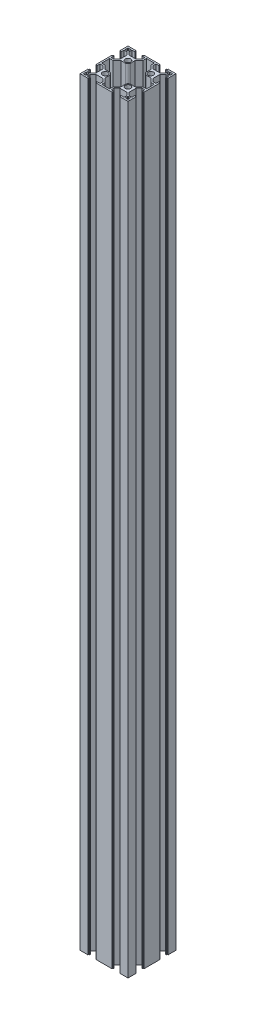
SolidWorks part; units mm, degrees
ref_plane "Front Plane" through (0, 0, 0) normal (0, 0, 1) x (1, 0, 0)
ref_plane "Top Plane" through (0, 0, 0) normal (0, 1, 0) x (1, 0, 0)
ref_plane "Right Plane" through (0, 0, 0) normal (1, 0, 0) x (0, 0, -1)
sketch "Sketch1" plane through (0, 0, 0) normal (0, 1, 0) x (1, 0, 0)
  line L0 (0, 30) -> (0, -30) construction
  line L1 (-30, -30) -> (30, -30)
  line L2 (-30, -30) -> (-30, 30)
  line L3 (-30, 30) -> (30, 30)
  line L4 (30, -30) -> (30, 30)
  line L5 (-30, -30) -> (30, 30) construction
  line L6 (-30, 30) -> (30, -30) construction
  line L7 (-30, 0) -> (30, 0) construction
  line L8 (-23.05, -28) -> (-6.95, -28)
  line L9 (-6.95, -28) -> (-6.95, -24.4)
  line L10 (-6.95, -24.4) -> (-10.615, -20.8)
  line L11 (-10.615, -20.8) -> (-19.385, -20.8)
  line L12 (-19.385, -20.8) -> (-23.05, -24.4)
  line L13 (-23.05, -24.4) -> (-23.05, -28)
  line L14 (10.615, -20.8) -> (19.385, -20.8)
  line L15 (6.95, -24.4) -> (10.615, -20.8)
  line L16 (6.95, -28) -> (6.95, -24.4)
  line L17 (23.05, -28) -> (6.95, -28)
  line L18 (23.05, -24.4) -> (23.05, -28)
  line L19 (19.385, -20.8) -> (23.05, -24.4)
  line L20 (19.385, 20.8) -> (23.05, 24.4)
  line L21 (23.05, 24.4) -> (23.05, 28)
  line L22 (23.05, 28) -> (6.95, 28)
  line L23 (6.95, 28) -> (6.95, 24.4)
  line L24 (6.95, 24.4) -> (10.615, 20.8)
  line L25 (10.615, 20.8) -> (19.385, 20.8)
  line L26 (-23.05, 24.4) -> (-23.05, 28)
  line L27 (-19.385, 20.8) -> (-23.05, 24.4)
  line L28 (-10.615, 20.8) -> (-19.385, 20.8)
  line L29 (-6.95, 24.4) -> (-10.615, 20.8)
  line L30 (-6.95, 28) -> (-6.95, 24.4)
  line L31 (-23.05, 28) -> (-6.95, 28)
  line L32 (-20.8, 19.385) -> (-24.4, 23.05)
  line L33 (-24.4, 23.05) -> (-28, 23.05)
  line L34 (-28, 23.05) -> (-28, 6.95)
  line L35 (-28, 6.95) -> (-24.4, 6.95)
  line L36 (-24.4, 6.95) -> (-20.8, 10.615)
  line L37 (-20.8, 10.615) -> (-20.8, 19.385)
  line L38 (-24.4, -23.05) -> (-28, -23.05)
  line L39 (-20.8, -19.385) -> (-24.4, -23.05)
  line L40 (-20.8, -10.615) -> (-20.8, -19.385)
  line L41 (-24.4, -6.95) -> (-20.8, -10.615)
  line L42 (-28, -6.95) -> (-24.4, -6.95)
  line L43 (-28, -23.05) -> (-28, -6.95)
  line L44 (20.8, -19.385) -> (24.4, -23.05)
  line L45 (24.4, -23.05) -> (28, -23.05)
  line L46 (28, -23.05) -> (28, -6.95)
  line L47 (28, -6.95) -> (24.4, -6.95)
  line L48 (24.4, -6.95) -> (20.8, -10.615)
  line L49 (20.8, -10.615) -> (20.8, -19.385)
  line L50 (24.4, 23.05) -> (28, 23.05)
  line L51 (20.8, 19.385) -> (24.4, 23.05)
  line L52 (20.8, 10.615) -> (20.8, 19.385)
  line L53 (24.4, 6.95) -> (20.8, 10.615)
  line L54 (28, 6.95) -> (24.4, 6.95)
  line L55 (28, 23.05) -> (28, 6.95)
  point P0 (0, 0)
  dimension "D1" = 60
  dimension "D2" = 16.1
  dimension "D3" = 8.77
  dimension "D4" = 3.6
  dimension "D5" = 7.2
  dimension "D6" = 2
  dimension "D7" = 6.95
extrude "Boss-Extrude1" add sketch "Sketch1" along normal blind 950
sketch "Sketch2" plane through (0, 950, 0) normal (0, 1, 0) x (1, 0, 0)
  line L0 (-19.1, -28) -> (-19.1, -29)
  line L1 (-23.05, -28) -> (-6.95, -28) construction
  line L2 (-30, -30) -> (30, -30) construction
  line L3 (-10.9, -28) -> (-10.9, -29)
  line L4 (-10.9, -29) -> (-9.9, -29)
  line L5 (-9.9, -29) -> (-9.9, -30)
  line L6 (-19.1, -29) -> (-20.1, -29)
  line L7 (-20.1, -29) -> (-20.1, -30)
  line L8 (-19.1, -28) -> (-10.9, -28)
  line L9 (-20.1, -30) -> (-9.9, -30)
  dimension "D1" = 8.2
  dimension "D2" = 3.95
  dimension "D3" = 1
  dimension "D4" = 1
extrude "Cut-Extrude1" cut sketch "Sketch2" against normal through all
mirror "Mirror1" about plane through (0, 0, 0) normal (1, 0, 0) of "Cut-Extrude1"
ref_axis "Axis1" through (0, 1050, 0) along (0, -1, 0)
pattern_circular "CirPattern1" count 4 over 360 about axis through (0, 1050, 0) along (0, -1, 0) of "Cut-Extrude1", "Mirror1"
sketch "Sketch4" plane through (0, 950, 0) normal (0, 1, 0) x (1, 0, 0)
  line L0 (19.385, 18.8) -> (9.797, 18.8) construction
  line L1 (-18.8, 18.8) -> (-18.8, 9.797)
  line L2 (18.8, -19.385) -> (18.8, -9.797) construction
  line L3 (28, 4.95) -> (28, -4.95)
  line L4 (-18.8, -9.797) -> (-18.8, -19.385) construction
  line L5 (4.95, -28) -> (-4.95, -28)
  line L6 (-9.797, 18.8) -> (-9.797, 13.197)
  line L7 (-28, -4.95) -> (-28, 4.95)
  line L8 (-18.8, 9.797) -> (-23.5611, 4.95)
  line L9 (-23.5611, 4.95) -> (-28, 4.95)
  line L10 (18.8, 18.8) -> (9.797, 18.8)
  line L11 (9.797, 18.8) -> (4.95, 23.5611)
  line L12 (4.95, 23.5611) -> (4.95, 28)
  line L13 (4.95, 28) -> (4.95, 28)
  line L14 (4.95, 28) -> (4.95, 28)
  line L15 (4.95, 28) -> (4.95, 28)
  line L16 (4.95, 28) -> (4.95, 28)
  line L17 (4.95, 28) -> (-4.95, 28)
  line L18 (-4.95, 28) -> (-4.95, 28)
  line L19 (-4.95, 28) -> (-4.95, 28)
  line L20 (-4.95, 28) -> (-4.95, 28)
  line L21 (-4.95, 28) -> (-4.95, 28)
  line L22 (-4.95, 28) -> (-4.95, 23.5611)
  line L23 (-4.95, 23.5611) -> (-9.797, 18.8)
  line L24 (-9.797, 18.8) -> (-18.8, 18.8)
  line L25 (28, 4.95) -> (23.5611, 4.95)
  line L26 (23.5611, 4.95) -> (18.8, 9.797)
  line L27 (18.8, 9.797) -> (18.8, 18.8)
  line L28 (18.8, -18.8) -> (18.8, -9.797)
  line L29 (18.8, -9.797) -> (23.5611, -4.95)
  line L30 (23.5611, -4.95) -> (28, -4.95)
  line L31 (4.95, -28) -> (4.95, -23.5611)
  line L32 (4.95, -23.5611) -> (9.797, -18.8)
  line L33 (9.797, -18.8) -> (18.8, -18.8)
  line L34 (-18.8, -18.8) -> (-9.797, -18.8)
  line L35 (-9.797, -18.8) -> (-4.95, -23.5611)
  line L36 (-4.95, -23.5611) -> (-4.95, -28)
  line L37 (-28, -4.95) -> (-23.5611, -4.95)
  line L38 (-23.5611, -4.95) -> (-18.8, -9.797)
  line L39 (-18.8, -9.797) -> (-18.8, -18.8)
  line L40 (-9.797, 18.8) -> (-19.385, 18.8) construction
  line L41 (-18.8, 19.385) -> (-18.8, 9.797) construction
  line L42 (18.8, 9.797) -> (18.8, 19.385) construction
  line L43 (9.797, -18.8) -> (19.385, -18.8) construction
  line L44 (-19.385, -18.8) -> (-9.797, -18.8) construction
  line L45 (-13.197, 9.797) -> (-18.8, 9.797)
  line L46 (9.797, 18.8) -> (9.797, 13.197)
  line L47 (13.197, 9.797) -> (18.8, 9.797)
  line L48 (-18.8, -9.797) -> (-13.197, -9.797)
  line L49 (-9.797, -13.197) -> (-9.797, -18.8)
  line L50 (9.797, -18.8) -> (9.797, -13.197)
  line L51 (13.197, -9.797) -> (18.8, -9.797)
  line L52 (-27.5, -28) -> (-24.9, -28)
  line L53 (24.9, -28) -> (27.5, -28)
  line L54 (24.4, -27.5) -> (24.4, -24.9)
  line L55 (24.9, -24.4) -> (27.5, -24.4)
  line L56 (28, -27.5) -> (28, -24.9)
  line L57 (24.4, -28) -> (28, -24.4) construction
  line L58 (24.4, -24.4) -> (28, -28) construction
  line L59 (-28, -24.9) -> (-28, -27.5)
  line L60 (-27.5, -24.4) -> (-24.9, -24.4)
  line L61 (-24.4, -24.9) -> (-24.4, -27.5)
  line L62 (-28, 27.5) -> (-28, 24.9)
  line L63 (-24.9, 28) -> (-27.5, 28)
  line L64 (-24.4, 27.5) -> (-24.4, 24.9)
  line L65 (-24.9, 24.4) -> (-27.5, 24.4)
  line L66 (27.5, 28) -> (24.9, 28)
  line L67 (28, 24.9) -> (28, 27.5)
  line L68 (27.5, 24.4) -> (24.9, 24.4)
  line L69 (24.4, 24.9) -> (24.4, 27.5)
  line L116 (28, 19.1) -> (29, 19.1)
  line L117 (29, 19.1) -> (29, 20.1)
  line L118 (29, 20.1) -> (30, 20.1)
  line L119 (30, 20.1) -> (30, 30)
  line L120 (30, 30) -> (20.1, 30)
  line L121 (20.1, 30) -> (20.1, 29)
  line L122 (20.1, 29) -> (19.1, 29)
  line L123 (19.1, 29) -> (19.1, 28)
  line L124 (19.1, 28) -> (23.05, 28)
  line L125 (23.05, 28) -> (23.05, 24.4)
  line L126 (23.05, 24.4) -> (19.385, 20.8)
  line L127 (19.385, 20.8) -> (10.615, 20.8)
  line L128 (10.615, 20.8) -> (6.95, 24.4)
  line L129 (6.95, 24.4) -> (6.95, 28)
  line L130 (6.95, 28) -> (10.9, 28)
  line L131 (10.9, 28) -> (10.9, 29)
  line L132 (10.9, 29) -> (9.9, 29)
  line L133 (9.9, 29) -> (9.9, 30)
  line L134 (9.9, 30) -> (-9.9, 30)
  line L135 (-9.9, 30) -> (-9.9, 29)
  line L136 (-9.9, 29) -> (-10.9, 29)
  line L137 (-10.9, 29) -> (-10.9, 28)
  line L138 (-10.9, 28) -> (-6.95, 28)
  line L139 (-6.95, 28) -> (-6.95, 24.4)
  line L140 (-6.95, 24.4) -> (-10.615, 20.8)
  line L141 (-10.615, 20.8) -> (-19.385, 20.8)
  line L142 (-19.385, 20.8) -> (-23.05, 24.4)
  line L143 (-23.05, 24.4) -> (-23.05, 28)
  line L144 (-23.05, 28) -> (-19.1, 28)
  line L145 (-19.1, 28) -> (-19.1, 29)
  line L146 (-19.1, 29) -> (-20.1, 29)
  line L147 (-20.1, 29) -> (-20.1, 30)
  line L148 (-20.1, 30) -> (-30, 30)
  line L149 (-30, 30) -> (-30, 20.1)
  line L150 (-30, 20.1) -> (-29, 20.1)
  line L151 (-29, 20.1) -> (-29, 19.1)
  line L152 (-29, 19.1) -> (-28, 19.1)
  line L153 (-28, 19.1) -> (-28, 23.05)
  line L154 (-28, 23.05) -> (-24.4, 23.05)
  line L155 (-24.4, 23.05) -> (-20.8, 19.385)
  line L156 (-20.8, 19.385) -> (-20.8, 10.615)
  line L157 (-20.8, 10.615) -> (-24.4, 6.95)
  line L158 (-24.4, 6.95) -> (-28, 6.95)
  line L159 (-28, 6.95) -> (-28, 10.9)
  line L160 (-28, 10.9) -> (-29, 10.9)
  line L161 (-29, 10.9) -> (-29, 9.9)
  line L162 (-29, 9.9) -> (-30, 9.9)
  line L163 (-30, 9.9) -> (-30, -9.9)
  line L164 (-30, -9.9) -> (-29, -9.9)
  line L165 (-29, -9.9) -> (-29, -10.9)
  line L166 (-29, -10.9) -> (-28, -10.9)
  line L167 (-28, -10.9) -> (-28, -6.95)
  line L168 (-28, -6.95) -> (-24.4, -6.95)
  line L169 (-24.4, -6.95) -> (-20.8, -10.615)
  line L170 (-20.8, -10.615) -> (-20.8, -19.385)
  line L171 (-20.8, -19.385) -> (-24.4, -23.05)
  line L172 (-24.4, -23.05) -> (-28, -23.05)
  line L173 (-28, -23.05) -> (-28, -19.1)
  line L174 (-28, -19.1) -> (-29, -19.1)
  line L175 (-29, -19.1) -> (-29, -20.1)
  line L176 (-29, -20.1) -> (-30, -20.1)
  line L177 (-30, -20.1) -> (-30, -30)
  line L178 (-30, -30) -> (-20.1, -30)
  line L179 (-20.1, -30) -> (-20.1, -29)
  line L180 (-20.1, -29) -> (-19.1, -29)
  line L181 (-19.1, -29) -> (-19.1, -28)
  line L182 (-19.1, -28) -> (-23.05, -28)
  line L183 (-23.05, -28) -> (-23.05, -24.4)
  line L184 (-23.05, -24.4) -> (-19.385, -20.8)
  line L185 (-19.385, -20.8) -> (-10.615, -20.8)
  line L186 (-10.615, -20.8) -> (-6.95, -24.4)
  line L187 (-6.95, -24.4) -> (-6.95, -28)
  line L188 (-6.95, -28) -> (-10.9, -28)
  line L189 (-10.9, -28) -> (-10.9, -29)
  line L190 (-10.9, -29) -> (-9.9, -29)
  line L191 (-9.9, -29) -> (-9.9, -30)
  line L192 (-9.9, -30) -> (9.9, -30)
  line L193 (9.9, -30) -> (9.9, -29)
  line L194 (9.9, -29) -> (10.9, -29)
  line L195 (10.9, -29) -> (10.9, -28)
  line L196 (10.9, -28) -> (6.95, -28)
  line L197 (6.95, -28) -> (6.95, -24.4)
  line L198 (6.95, -24.4) -> (10.615, -20.8)
  line L199 (10.615, -20.8) -> (19.385, -20.8)
  line L200 (19.385, -20.8) -> (23.05, -24.4)
  line L201 (23.05, -24.4) -> (23.05, -28)
  line L202 (23.05, -28) -> (19.1, -28)
  line L203 (19.1, -28) -> (19.1, -29)
  line L204 (19.1, -29) -> (20.1, -29)
  line L205 (20.1, -29) -> (20.1, -30)
  line L206 (20.1, -30) -> (30, -30)
  line L207 (30, -30) -> (30, -20.1)
  line L208 (30, -20.1) -> (29, -20.1)
  line L209 (29, -20.1) -> (29, -19.1)
  line L210 (29, -19.1) -> (28, -19.1)
  line L211 (28, -19.1) -> (28, -23.05)
  line L212 (28, -23.05) -> (24.4, -23.05)
  line L213 (24.4, -23.05) -> (20.8, -19.385)
  line L214 (20.8, -19.385) -> (20.8, -10.615)
  line L215 (20.8, -10.615) -> (24.4, -6.95)
  line L216 (24.4, -6.95) -> (28, -6.95)
  line L217 (28, -6.95) -> (28, -10.9)
  line L218 (28, -10.9) -> (29, -10.9)
  line L219 (29, -10.9) -> (29, -9.9)
  line L220 (29, -9.9) -> (30, -9.9)
  line L221 (30, -9.9) -> (30, 9.9)
  line L222 (30, 9.9) -> (29, 9.9)
  line L223 (29, 9.9) -> (29, 10.9)
  line L224 (29, 10.9) -> (28, 10.9)
  line L225 (28, 10.9) -> (28, 6.95)
  line L226 (28, 6.95) -> (24.4, 6.95)
  line L227 (24.4, 6.95) -> (20.8, 10.615)
  line L228 (20.8, 10.615) -> (20.8, 19.385)
  line L229 (20.8, 19.385) -> (24.4, 23.05)
  line L230 (24.4, 23.05) -> (28, 23.05)
  line L231 (28, 23.05) -> (28, 19.1)
  line L232 (28, 19.1) -> (29, 19.1)
  line L233 (29, 19.1) -> (29, 20.1)
  line L234 (29, 20.1) -> (30, 20.1)
  line L235 (30, 20.1) -> (30, 30)
  line L236 (30, 30) -> (20.1, 30)
  line L237 (20.1, 30) -> (20.1, 29)
  line L238 (20.1, 29) -> (19.1, 29)
  line L239 (19.1, 29) -> (19.1, 28)
  line L240 (19.1, 28) -> (23.05, 28)
  line L241 (23.05, 28) -> (23.05, 24.4)
  line L242 (23.05, 24.4) -> (19.385, 20.8)
  line L243 (19.385, 20.8) -> (10.615, 20.8)
  line L244 (10.615, 20.8) -> (6.95, 24.4)
  line L245 (6.95, 24.4) -> (6.95, 28)
  line L246 (6.95, 28) -> (10.9, 28)
  line L247 (10.9, 28) -> (10.9, 29)
  line L248 (10.9, 29) -> (9.9, 29)
  line L249 (9.9, 29) -> (9.9, 30)
  line L250 (9.9, 30) -> (-9.9, 30)
  line L251 (-9.9, 30) -> (-9.9, 29)
  line L252 (-9.9, 29) -> (-10.9, 29)
  line L253 (-10.9, 29) -> (-10.9, 28)
  line L254 (-10.9, 28) -> (-6.95, 28)
  line L255 (-6.95, 28) -> (-6.95, 24.4)
  line L256 (-6.95, 24.4) -> (-10.615, 20.8)
  line L257 (-10.615, 20.8) -> (-19.385, 20.8)
  line L258 (-19.385, 20.8) -> (-23.05, 24.4)
  line L259 (-23.05, 24.4) -> (-23.05, 28)
  line L260 (-23.05, 28) -> (-19.1, 28)
  line L261 (-19.1, 28) -> (-19.1, 29)
  line L262 (-19.1, 29) -> (-20.1, 29)
  line L263 (-20.1, 29) -> (-20.1, 30)
  line L264 (-20.1, 30) -> (-30, 30)
  line L265 (-30, 30) -> (-30, 20.1)
  line L266 (-30, 20.1) -> (-29, 20.1)
  line L267 (-29, 20.1) -> (-29, 19.1)
  line L268 (-29, 19.1) -> (-28, 19.1)
  line L269 (-28, 19.1) -> (-28, 23.05)
  line L270 (-28, 23.05) -> (-24.4, 23.05)
  line L271 (-24.4, 23.05) -> (-20.8, 19.385)
  line L272 (-20.8, 19.385) -> (-20.8, 10.615)
  line L273 (-20.8, 10.615) -> (-24.4, 6.95)
  line L274 (-24.4, 6.95) -> (-28, 6.95)
  line L275 (-28, 6.95) -> (-28, 10.9)
  line L276 (-28, 10.9) -> (-29, 10.9)
  line L277 (-29, 10.9) -> (-29, 9.9)
  line L278 (-29, 9.9) -> (-30, 9.9)
  line L279 (-30, 9.9) -> (-30, -9.9)
  line L280 (-30, -9.9) -> (-29, -9.9)
  line L281 (-29, -9.9) -> (-29, -10.9)
  line L282 (-29, -10.9) -> (-28, -10.9)
  line L283 (-28, -10.9) -> (-28, -6.95)
  line L284 (-28, -6.95) -> (-24.4, -6.95)
  line L285 (-24.4, -6.95) -> (-20.8, -10.615)
  line L286 (-20.8, -10.615) -> (-20.8, -19.385)
  line L287 (-20.8, -19.385) -> (-24.4, -23.05)
  line L288 (-24.4, -23.05) -> (-28, -23.05)
  line L289 (-28, -23.05) -> (-28, -19.1)
  line L290 (-28, -19.1) -> (-29, -19.1)
  line L291 (-29, -19.1) -> (-29, -20.1)
  line L292 (-29, -20.1) -> (-30, -20.1)
  line L293 (-30, -20.1) -> (-30, -30)
  line L294 (-30, -30) -> (-20.1, -30)
  line L295 (-20.1, -30) -> (-20.1, -29)
  line L296 (-20.1, -29) -> (-19.1, -29)
  line L297 (-19.1, -29) -> (-19.1, -28)
  line L298 (-19.1, -28) -> (-23.05, -28)
  line L299 (-23.05, -28) -> (-23.05, -24.4)
  line L300 (-23.05, -24.4) -> (-19.385, -20.8)
  line L301 (-19.385, -20.8) -> (-10.615, -20.8)
  line L302 (-10.615, -20.8) -> (-6.95, -24.4)
  line L303 (-6.95, -24.4) -> (-6.95, -28)
  line L304 (-6.95, -28) -> (-10.9, -28)
  line L305 (-10.9, -28) -> (-10.9, -29)
  line L306 (-10.9, -29) -> (-9.9, -29)
  line L307 (-9.9, -29) -> (-9.9, -30)
  line L308 (-9.9, -30) -> (9.9, -30)
  line L309 (9.9, -30) -> (9.9, -29)
  line L310 (9.9, -29) -> (10.9, -29)
  line L311 (10.9, -29) -> (10.9, -28)
  line L312 (10.9, -28) -> (6.95, -28)
  line L313 (6.95, -28) -> (6.95, -24.4)
  line L314 (6.95, -24.4) -> (10.615, -20.8)
  line L315 (10.615, -20.8) -> (19.385, -20.8)
  line L316 (19.385, -20.8) -> (23.05, -24.4)
  line L317 (23.05, -24.4) -> (23.05, -28)
  line L318 (23.05, -28) -> (19.1, -28)
  line L319 (19.1, -28) -> (19.1, -29)
  line L320 (19.1, -29) -> (20.1, -29)
  line L321 (20.1, -29) -> (20.1, -30)
  line L322 (20.1, -30) -> (30, -30)
  line L323 (30, -30) -> (30, -20.1)
  line L324 (30, -20.1) -> (29, -20.1)
  line L325 (29, -20.1) -> (29, -19.1)
  line L326 (29, -19.1) -> (28, -19.1)
  line L327 (28, -19.1) -> (28, -23.05)
  line L328 (28, -23.05) -> (24.4, -23.05)
  line L329 (24.4, -23.05) -> (20.8, -19.385)
  line L330 (20.8, -19.385) -> (20.8, -10.615)
  line L331 (20.8, -10.615) -> (24.4, -6.95)
  line L332 (24.4, -6.95) -> (28, -6.95)
  line L333 (28, -6.95) -> (28, -10.9)
  line L334 (28, -10.9) -> (29, -10.9)
  line L335 (29, -10.9) -> (29, -9.9)
  line L336 (29, -9.9) -> (30, -9.9)
  line L337 (30, -9.9) -> (30, 9.9)
  line L338 (30, 9.9) -> (29, 9.9)
  line L339 (29, 9.9) -> (29, 10.9)
  line L340 (29, 10.9) -> (28, 10.9)
  line L341 (28, 10.9) -> (28, 6.95)
  line L342 (28, 6.95) -> (24.4, 6.95)
  line L343 (24.4, 6.95) -> (20.8, 10.615)
  line L344 (20.8, 10.615) -> (20.8, 19.385)
  line L345 (20.8, 19.385) -> (24.4, 23.05)
  line L346 (24.4, 23.05) -> (28, 23.05)
  line L347 (28, 23.05) -> (28, 19.1)
  circle A0 centre (14.2985, 14.2985) radius 3.4
  arc A1 (13.197, -9.797) -> (9.797, -13.197) centre (13.197, -13.197) ccw
  arc A2 (-9.797, -13.197) -> (-13.197, -9.797) centre (-13.197, -13.197) ccw
  arc A3 (13.197, 9.797) -> (9.797, 13.197) centre (13.197, 13.197) cw
  arc A4 (-9.797, 13.197) -> (-13.197, 9.797) centre (-13.197, 13.197) cw
  circle A5 centre (14.2985, -14.2985) radius 3.4
  circle A6 centre (-14.2985, -14.2985) radius 3.4
  circle A7 centre (-14.2985, 14.2985) radius 3.4
  arc A8 (24.4, -27.5) -> (24.9, -28) centre (24.9, -27.5) ccw
  arc A9 (28, -27.5) -> (27.5, -28) centre (27.5, -27.5) cw
  arc A10 (28, -24.9) -> (27.5, -24.4) centre (27.5, -24.9) ccw
  arc A11 (24.4, -24.9) -> (24.9, -24.4) centre (24.9, -24.9) cw
  arc A12 (-27.5, -28) -> (-28, -27.5) centre (-27.5, -27.5) cw
  arc A13 (-27.5, -24.4) -> (-28, -24.9) centre (-27.5, -24.9) ccw
  arc A14 (-24.9, -24.4) -> (-24.4, -24.9) centre (-24.9, -24.9) cw
  arc A15 (-24.9, -28) -> (-24.4, -27.5) centre (-24.9, -27.5) ccw
  arc A16 (-28, 27.5) -> (-27.5, 28) centre (-27.5, 27.5) cw
  arc A17 (-24.4, 27.5) -> (-24.9, 28) centre (-24.9, 27.5) ccw
  arc A18 (-24.4, 24.9) -> (-24.9, 24.4) centre (-24.9, 24.9) cw
  arc A19 (-28, 24.9) -> (-27.5, 24.4) centre (-27.5, 24.9) ccw
  arc A20 (27.5, 28) -> (28, 27.5) centre (27.5, 27.5) cw
  arc A21 (27.5, 24.4) -> (28, 24.9) centre (27.5, 24.9) ccw
  arc A22 (24.9, 24.4) -> (24.4, 24.9) centre (24.9, 24.9) cw
  arc A23 (24.9, 28) -> (24.4, 27.5) centre (24.9, 27.5) ccw
  point P102 (26.2, -26.2)
  point P104 (14.2985, 18.8)
  point P106 (18.8, 14.2985)
  point P140 (0, 0)
  point P239 (0, 0)
  dimension "D3" = 6.8
  dimension "D4" = 3.4
  dimension "D6" = 0.5
  dimension "D1" = 0
  dimension "D2" = 2
  dimension "D5" = 4
  dimension "D7" = 4
extrude "Cut-Extrude2" cut sketch "Sketch4" against normal blind 1000 contours L6 A4 L45 L8 L9 L7 L37 L38 L48 A2 L49 L35 L36 L5 L31 L32 L50 A1 L51 L29 L30 L3 L25 L26 L47 A3 L46 L11 L12 L17 L22 L23 | A7 | A0 | L66 A23 L69 A22 L68 A21 L67 A20 | L62 A19 L65 A18 L64 A17 L63 A16 | L52 A15 L61 A14 L60 A13 L59 A12 | A11 L54 A8 L53 A9 L56 A10 L55 | A6 | A5 region at (0, 950, 0) region at (-26.2, 950, 26.2) region at (26.2, 950, 26.2) region at (-26.2, 950, -26.2) region at (26.2, 950, -26.2) region at (14.2985, 950, -14.2985) region at (-14.2985, 950, -14.2985)
fillet "Fillet1" radius 0.2 16 edges at (28, 475, -19.1) (30, 475, -20.1) (29, 475, -20.1) (29, 475, -19.1) (28, 475, 10.9) (29, 475, 9.9) (28, 475, 19.1) (29, 475, 20.1) (30, 475, 20.1) (29, 475, 19.1) (29, 475, 10.9) (30, 475, 9.9) (30, 475, -9.9) (29, 475, -9.9) (29, 475, -10.9) (28, 475, -10.9)
fillet "Fillet2" radius 0.2 20 edges at (-20.1, 0, -29.5) (-20.1, 950, -29.5) (-20.1, 475, -29) (-19.6, 0, -29) (-19.1, 475, -29) (-19.6, 950, -29) (-9.9, 475, -30) (-10.9, 475, -28) (-10.9, 475, -29) (-9.9, 475, -29) (19.1, 475, -28) (19.1, 475, -29) (20.1, 475, -29) (20.1, 475, -30) (10.9, 475, -28) (10.9, 475, -29) (9.9, 475, -29) (9.9, 475, -30) (-19.1, 475, -28) (-20.1, 475, -30)
fillet "Fillet3" radius 0.2 14 edges at (-29, 475, 9.9) (-29, 475, -20.1) (-30, 475, -20.1) (-29, 475, -19.1) (-28, 475, -10.9) (-29, 475, -10.9) (-29, 475, -9.9) (-30, 475, -9.9) (-29, 475, 10.9) (-30, 475, 9.9) (-28, 475, 19.1) (-29, 475, 19.1) (-29, 475, 20.1) (-30, 475, 20.1)
fillet "Fillet4" radius 0.2 16 edges at (-19.1, 475, 28) (10.9, 475, 28) (19.1, 475, 28) (20.1, 475, 29) (-10.9, 475, 28) (-9.9, 475, 29) (9.9, 475, 29) (-20.1, 475, 29) (19.1, 475, 29) (20.1, 475, 30) (10.9, 475, 29) (9.9, 475, 30) (-9.9, 475, 30) (-10.9, 475, 29) (-19.1, 475, 29) (-20.1, 475, 30)
